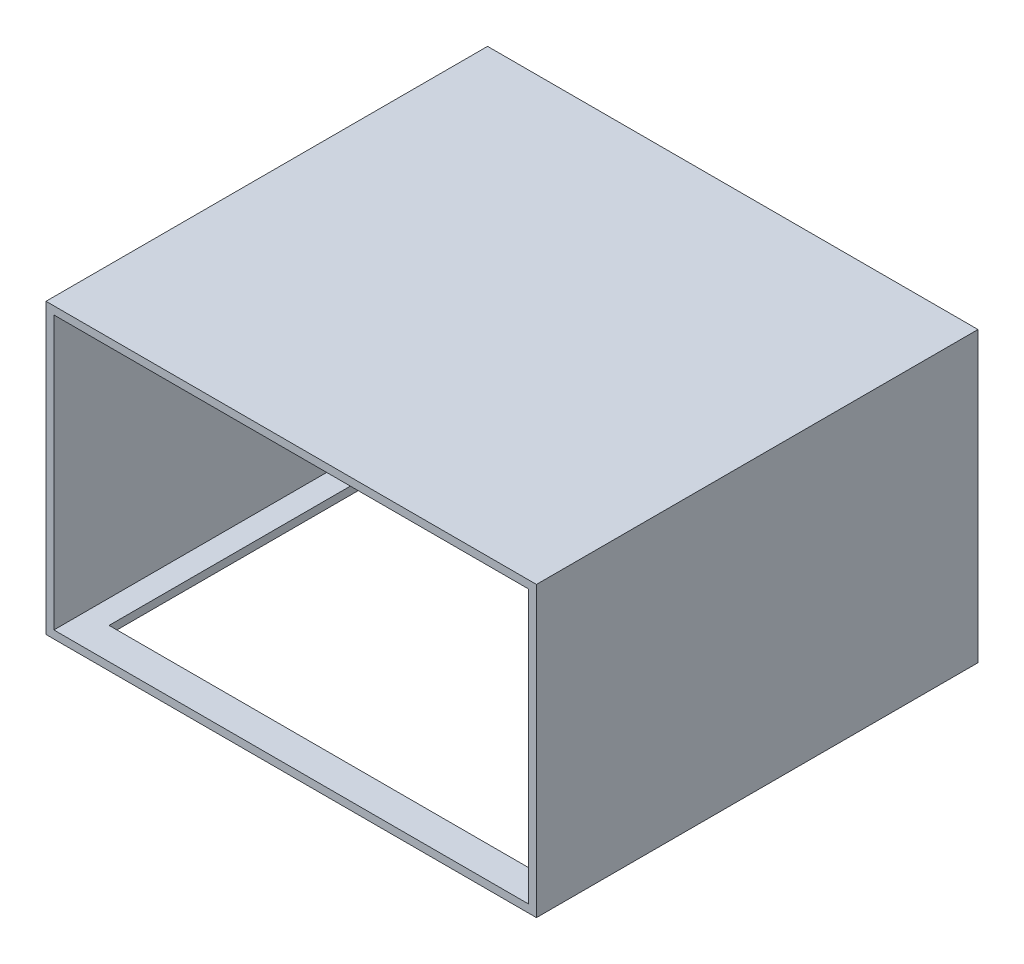
SolidWorks part; units mm, degrees
ref_plane "Front Plane" through (0, 0, 0) normal (0, 0, 1) x (1, 0, 0)
ref_plane "Top Plane" through (0, 0, 0) normal (0, 1, 0) x (1, 0, 0)
ref_plane "Right Plane" through (0, 0, 0) normal (1, 0, 0) x (0, 0, -1)
sketch "Sketch1" plane through (0, 0, 0) normal (0, 1, 0) x (1, 0, 0)
  line L1 (-14.9853, 125.3233) -> (-17.4853, 125.3233)
  line L2 (-14.9853, 125.3233) -> (-14.9853, -14.6767)
  line L3 (-14.9853, -14.6767) -> (-17.4853, -14.6767)
  line L4 (-17.4853, 125.3233) -> (-17.4853, -14.6767)
  line L5 (135.5147, -14.6767) -> (138.0147, -14.6767)
  line L6 (135.5147, -14.6767) -> (135.5147, 125.3233)
  line L7 (135.5147, 125.3233) -> (138.0147, 125.3233)
  line L8 (138.0147, -14.6767) -> (138.0147, 125.3233)
  dimension "D1" = 2.5
  dimension "D2" = 140
  dimension "D3" = 2.5
  dimension "D4" = 140
  dimension "D5" = 150.5
extrude "Boss-Extrude1" add sketch "Sketch1" along normal blind 86.5
sketch "Sketch2" plane through (0, 86.5, 0) normal (0, 1, 0) x (1, 0, 0)
  line L1 (-17.4853, -14.6767) -> (138.0147, -14.6767)
  line L2 (-17.4853, -14.6767) -> (-17.4853, 125.3233)
  line L3 (-17.4853, 125.3233) -> (138.0147, 125.3233)
  line L4 (138.0147, -14.6767) -> (138.0147, 125.3233)
extrude "Boss-Extrude2" add sketch "Sketch2" along normal blind 2.5
sketch "Sketch3" plane through (0, 0, 0) normal (0, 1, 0) x (1, 0, 0)
  line L1 (-17.4853, 125.3233) -> (138.0147, 125.3233)
  line L2 (-17.4853, 125.3233) -> (-17.4853, -14.6767)
  line L3 (-17.4853, -14.6767) -> (138.0147, -14.6767)
  line L4 (138.0147, 125.3233) -> (138.0147, -14.6767)
  line L5 (-7.4853, 115.3233) -> (128.0147, 115.3233)
  line L6 (-7.4853, 115.3233) -> (-7.4853, -4.6767)
  line L7 (-7.4853, -4.6767) -> (128.0147, -4.6767)
  line L8 (128.0147, 115.3233) -> (128.0147, -4.6767)
  dimension "D1" = 10
  dimension "D2" = 10
  dimension "D3" = 10
  dimension "D4" = 10
extrude "Boss-Extrude3" add sketch "Sketch3" against normal blind 2.5
